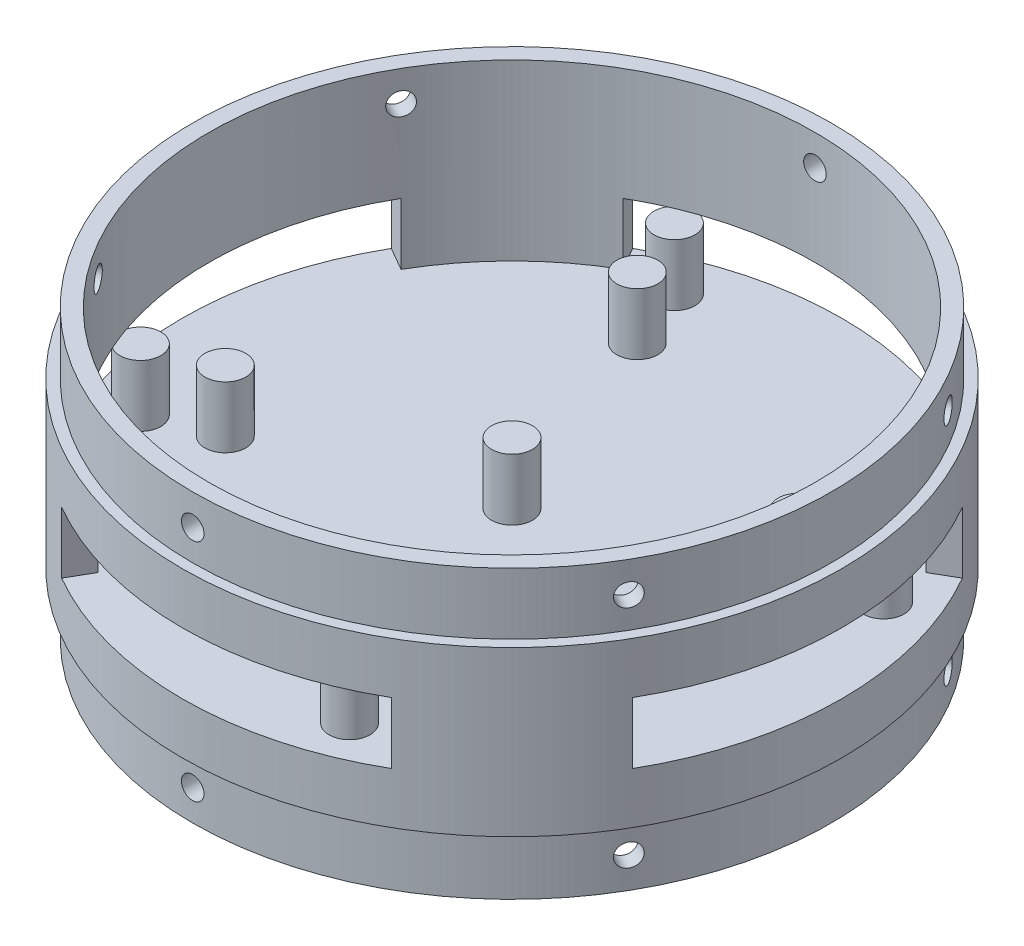
SolidWorks part; units mm, degrees
ref_plane "Front Plane" through (0, 0, 0) normal (0, 0, 1) x (1, 0, 0)
ref_plane "Top Plane" through (0, 0, 0) normal (0, 1, 0) x (1, 0, 0)
ref_plane "Right Plane" through (0, 0, 0) normal (1, 0, 0) x (0, 0, -1)
sketch "Sketch1" plane through (0, 0, 0) normal (0, 1, 0) x (1, 0, 0)
  line L0 (0, 0) -> (-25.5524, 44.2581)
  line L1 (0, 0) -> (25.5524, 44.2581)
  line L2 (0, 0) -> (0, 72.1431) construction
  circle A0 centre (0, 0) radius 51.1048
  circle A1 centre (0, 0) radius 46.99
  circle A2 centre (0, 0) radius 49.5173
  dimension "D1" = 102.2096
  dimension "D2" = 93.98
  dimension "D3" = 99.0346
  dimension "D4" = 60
extrude "Boss-Extrude1" add sketch "Sketch1" along normal blind 25.4 contours L2 A2 L1 A0 | L2 A1 L1 A2 | L2 A2 L1 A1 | L2 A0 L1 A2 | A2 L2 A1 L0 | A0 L2 A2 L0 | A2 L2 A0 L0 | A1 L2 A2 L0 region at (-24.1722, 0, 41.8675) region at (-12.3496, 0, -46.0894) region at (12.3496, 0, -46.0894) region at (-25.4576, 0, 44.0938) region at (-12.8743, 0, -48.0475) region at (12.8743, 0, -48.0475)
ref_plane "Plane1" through (0, 12.7, 0) normal (0, 1, 0) x (1, 0, 0)
extrude "Boss-Extrude2" add sketch "Sketch1<3>" along normal blind 9.525 from surface contours A2 L2 A1 L0 | L2 A2 L1 A1 | L2 A1 L1 A2 | A1 L2 A2 L0 region at (-24.1722, 0, 41.8675) region at (-12.3496, 0, -46.0894) region at (12.3496, 0, -46.0894) starting at face at (0, 25.4, 46.99)
sketch "Sketch1<3>" plane through (0, 0, 0) normal (0, 1, 0) x (1, 0, 0) same geometry as "Sketch1"
extrude "Boss-Extrude3" add sketch "Sketch1<4>" against normal blind 9.525 contours A2 L2 A1 L0 | A1 L2 A2 L0 | L2 A1 L1 A2 | L2 A2 L1 A1 region at (-24.1722, 0, 41.8675) region at (-12.3496, 0, -46.0894) region at (12.3496, 0, -46.0894)
sketch "Sketch1<4>" plane through (0, 0, 0) normal (0, 1, 0) x (1, 0, 0) same geometry as "Sketch1"
ref_plane "Plane2" through (0, 0, -49.5173) normal (0, 0, -1) x (-1, 0, 0)
ref_axis "Axis1" through (0, 0, 0) along (0, 1, 0)
sketch "Sketch3" plane through (0, 0, -49.5173) normal (0, 0, -1) x (-1, 0, 0)
  line L0 (49.5173, 0) -> (-49.5173, 0) construction
  line L1 (-49.5173, -9.525) -> (49.5173, -9.525) construction
  line L2 (49.5173, 25.4) -> (-49.5173, 25.4) construction
  line L3 (49.5173, 34.925) -> (-49.5173, 34.925) construction
  line L4 (49.5173, 0) -> (-49.5173, 0)
  line L5 (-49.5173, -9.525) -> (49.5173, -9.525)
  line L6 (49.5173, 25.4) -> (-49.5173, 25.4)
  line L7 (49.5173, 34.925) -> (-49.5173, 34.925)
  line L8 (0, 34.925) -> (0, 25.4)
  line L9 (0, 0) -> (0, -9.525)
  circle A0 centre (0, 30.1625) radius 1.75
  circle A1 centre (0, -4.7625) radius 1.75
  point P12 (0, 30.1625)
  point P13 (0, -4.7625)
  point P14 (-77.5445, 179.1871)
  dimension "D1" = 3.5
extrude "Cut-Extrude2" cut sketch "Sketch3" against normal up to next contours L8 A0 | L8 A0 | L9 A1 | L9 A1 region at (-0.7427, 30.1625, -49.5173) region at (0.7427, 30.1625, -49.5173) region at (-0.7427, -4.7625, -49.5173) region at (0.7427, -4.7625, -49.5173)
extrude "Cut-Extrude3" cut sketch "Sketch1<7>" against normal mid plane 9.525 from surface contours L2 A1 L1 A2 | A1 L2 A2 L0 | A2 L2 A0 L0 | L2 A2 L1 A0 region at (-12.3496, 0, -46.0894) region at (12.3496, 0, -46.0894) region at (-12.8743, 0, -48.0475) region at (12.8743, 0, -48.0475) starting at plane "Plane1"
sketch "Sketch1<7>" plane through (0, 0, 0) normal (0, 1, 0) x (1, 0, 0) same geometry as "Sketch1"
pattern_circular "CirPattern2" count 4 over 360 about axis through (0, 0, 0) along (0, 1, 0) of "Cut-Extrude3"
pattern_circular "CirPattern3" count 6 over 360 about axis through (0, 0, 0) along (0, 1, 0) of "Cut-Extrude2"
ref_plane "Plane3" through (0, 7.9375, 0) normal (0, 1, 0) x (1, 0, 0)
sketch "Sketch4" plane through (0, 7.9375, 0) normal (0, 1, 0) x (1, 0, 0)
  line L0 (-44.2581, 25.5524) -> (-40.6945, 23.495) construction
  line L1 (-44.2581, 25.5524) -> (-40.6945, 23.495)
  circle A0 centre (0, 0) radius 46.99
extrude "Boss-Extrude4" add sketch "Sketch4" against normal blind 6.35 contours A0 region at (0, 7.9375, 0)
sketch "Sketch5" plane through (0, 7.9375, 0) normal (0, 1, 0) x (1, 0, 0)
  line L0 (-25.5524, 44.2581) -> (-23.495, 40.6945) construction
  line L1 (-16.2113, 41.3884) -> (0, 0) construction
  circle A0 centre (-16.2113, 41.3884) radius 3.175
  circle A2 centre (0, 0) radius 3.175
  circle A3 centre (-12.5058, 31.9282) radius 3.175
  dimension "D1" = 6.35
  dimension "D4" = 6.35
  dimension "D5" = 6.35
  dimension "D2" = 44.45
  dimension "D3" = 6.6548
  dimension "D6" = 34.29
extrude "Boss-Extrude5" add sketch "Sketch5" along normal blind 9.525
pattern_circular "CirPattern4" count 4 over 360 about axis through (0, 7.9375, 0) along (0, 1, 0) of "Boss-Extrude5"
equation "\"AB_Coupler_OD_Length\"= 1in"
equation "\"AB_Coupling_Section_Length\"= 0.375in"
equation "\"AB_Coupler_Length\"= \"AB_Coupler_OD_Length\" + \"AB_Coupling_Section_Length\" * 2"
equation "\"D1@Boss-Extrude2\"=\"AB_Coupling_Section_Length\""
equation "\"D1@Boss-Extrude3\"=\"AB_Coupling_Section_Length\""
equation "\"D1@Boss-Extrude1\" = \"AB_Coupler_OD_Length\""
equation "\"Cutout_Angle\" = 60"
equation "\"AB_Coupler_Num_Screws\"= 6"
equation "\"Num_Cutouts\" = 4"
equation "\"D4@Sketch1\"=\"Cutout_Angle\""
equation "\"D1@CirPattern2\"=\"Num_Cutouts\""
equation "\"D1@CirPattern3\"=\"AB_Coupler_Num_Screws\""
equation "\"AB_Coupler_OD\"= 4.024in"
equation "\"AB_Coupler_ID\"= 3.7in"
equation "\"AB_Coupler_Surface_Diameter\"= 3.899in"
equation "\"D3@Sketch1\"=\"AB_Coupler_Surface_Diameter\""
equation "\"D2@Sketch1\"=\"AB_Coupler_ID\""
equation "\"D1@Sketch1\"=\"AB_Coupler_OD\""
equation "\"AB_Coupling_Screw_Diameter\"= 0.1065in"
equation "\"Bodytube_OD\"= 4.024in"
equation "\"D2@Sketch5\" = \"Paddle_Pin_Radius\""
equation "\"Paddle_Pin_Offset\"= \"Body_Tube_OD\" / 2 - \"Paddle_Pin_Radius\""
equation "\"D3@Sketch5\"=\"Paddle_Pin_Offset\""
equation "\"D1@CirPattern4\"=\"Num_Cutouts\""
equation "\"Bodytube_ID\"= 3.9"
equation "\"Paddle_Pin_Radius\"= 1.75"
equation "\"Body_Tube_OD\"= 4.024in"
equation "\"Body_Tube_ID\"= 3.90in"
equation "\"Coupler_OD\" = 3.899in"
equation "\"Coupler_ID\" = 3.755in"
